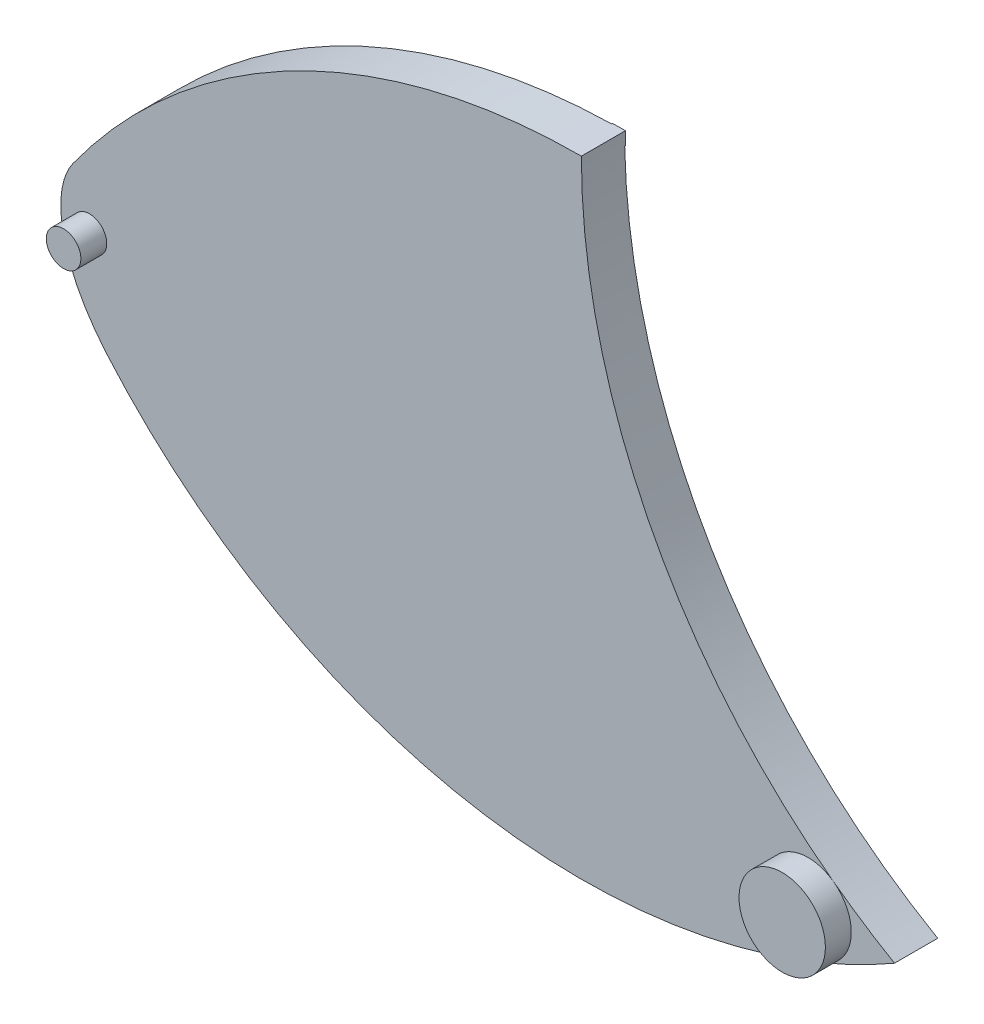
SolidWorks part; units mm, degrees
ref_plane "Piano frontale" through (0, 0, 0) normal (0, 0, 1) x (1, 0, 0)
ref_plane "Piano superiore" through (0, 0, 0) normal (0, 1, 0) x (1, 0, 0)
ref_plane "Piano destro" through (0, 0, 0) normal (1, 0, 0) x (0, 0, -1)
sketch "Schizzo1" plane through (0, 0, 0) normal (0, 0, 1) x (1, 0, 0)
  circle A0 centre (0, 0) radius 72.5 construction
  circle A1 centre (0, -72.5) radius 72.5 construction
  circle A2 centre (72.5, 0) radius 72.5 construction
  arc A3 (-62.7868, -36.25) -> (0, 0) centre (0, -72.5) cw
  arc A4 (36.25, -62.7868) -> (0, 0) centre (72.5, 0) cw
  arc A5 (36.25, -62.7868) -> (-62.7868, -36.25) centre (0, 0) cw
  dimension "D2" = 145
extrude "Estrusione-Estrusione1" add sketch "Schizzo1" along normal blind 5
sketch "Schizzo2" plane through (0, 0, 5) normal (0, 0, 1) x (1, 0, 0)
  circle A3 centre (-56.9402, -36.25) radius 2
  arc A6 (-56.9402, -36.25) -> (26.25, -62.1867) centre (0, 0) ccw
  arc A7 (-4.8272, -5.1728) -> (26.25, -62.1867) centre (72.5, 0) ccw
  arc A8 (-4.8272, -5.1728) -> (-56.9402, -36.25) centre (0, -72.5) ccw
  arc A9 (-56.9402, -36.25) -> (26.25, -62.1867) centre (0, 0) ccw construction
  arc A10 (-4.8272, -5.1728) -> (26.25, -62.1867) centre (72.5, 0) ccw construction
  arc A11 (-4.8272, -5.1728) -> (-56.9402, -36.25) centre (0, -72.5) ccw construction
  dimension "D2" = 4
  dimension "D1" = 5
sketch "Schizzo3" plane through (0, 0, 5) normal (0, 0, 1) x (1, 0, 0)
  circle A3 centre (26.25, -62.1867) radius 2.25
  arc A6 (-56.9402, -36.25) -> (26.25, -62.1867) centre (0, 0) ccw
  arc A7 (-4.8272, -5.1728) -> (26.25, -62.1867) centre (72.5, 0) ccw
  arc A8 (-4.8272, -5.1728) -> (-56.9402, -36.25) centre (0, -72.5) ccw
  arc A9 (-56.9402, -36.25) -> (26.25, -62.1867) centre (0, 0) ccw construction
  arc A10 (-4.8272, -5.1728) -> (26.25, -62.1867) centre (72.5, 0) ccw construction
  arc A11 (-4.8272, -5.1728) -> (-56.9402, -36.25) centre (0, -72.5) ccw construction
  dimension "D2" = 4.5
  dimension "D1" = 5
extrude "Estrusione-Estrusione3" add sketch "Schizzo2" along normal blind 3
extrude "Taglio-Estrusione2" cut sketch "Schizzo3" against normal blind 5
fillet "Raccordo2" radius 12 1 edges at (-62.7868, -36.25, 2.5) second distance 16 first distance on face at (-33.8217, -13.9191, 2.5)
sketch "Schizzo4" plane through (0, 0, 5) normal (0, 0, 1) x (1, 0, 0)
  circle A0 centre (26.25, -62.1867) radius 5
  dimension "D1" = 10
extrude "Estrusione-Estrusione4" add sketch "Schizzo4" along normal blind 3
sketch "Schizzo5" plane through (0, 0, 5) normal (0, 0, 1) x (1, 0, 0)
  arc A0 (-1.4999, -0.0155) -> (0.0155, -1.4999) centre (0, 0) ccw
  arc A1 (0, 0) -> (29.2339, -58.1747) centre (72.5, 0) ccw construction
  arc A2 (0, 0) -> (-58.8277, -30.1261) centre (0, -72.5) ccw construction
  arc A3 (0, 0) -> (0.0155, -1.4999) centre (72.5, 0) ccw
  arc A4 (0, 0) -> (-1.4999, -0.0155) centre (0, -72.5) ccw
  dimension "D1" = 1.5
extrude "Estrusione-Estrusione5" add sketch "Schizzo5" against normal blind 0.1 from surface starting at face at (28.5, -62.1867, 0)
